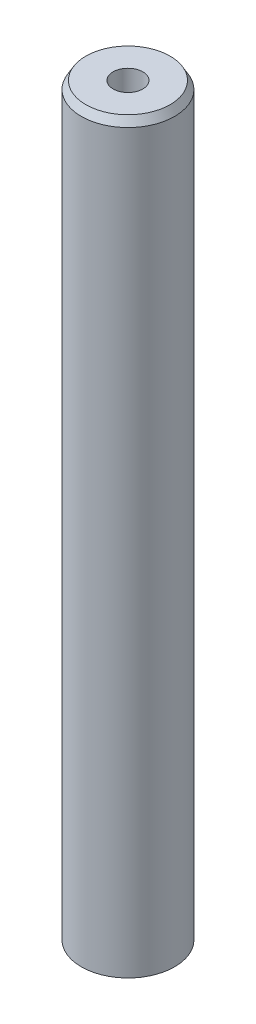
SolidWorks part; units mm, degrees
ref_plane "Front Plane" through (0, 0, 0) normal (0, 0, 1) x (1, 0, 0)
ref_plane "Top Plane" through (0, 0, 0) normal (0, 1, 0) x (1, 0, 0)
ref_plane "Right Plane" through (0, 0, 0) normal (1, 0, 0) x (0, 0, -1)
sketch "Sketch1" plane through (0, 0, 0) normal (0, 1, 0) x (1, 0, 0)
  circle A0 centre (0, 0) radius 22.5
  dimension "SHAFT_OD" = 45
extrude "Boss-Extrude1" add sketch "Sketch1" along normal blind 361.1083
sketch "Sketch2" plane through (0, 0, 0) normal (0, 1, 0) x (1, 0, 0)
  circle A0 centre (0, 0) radius 7.172
  dimension "BORE_D" = 14.3441
extrude "Cut-Extrude1" cut sketch "Sketch2" along normal through all
chamfer "Chamfer1" distance 3.8044 angle 30 2 edges at (0, 361.1083, 22.5) (0, 0, 22.5) first distance on face at (0, 361.1083, 22.5) first distance on face at (0, 0, 7.172)
